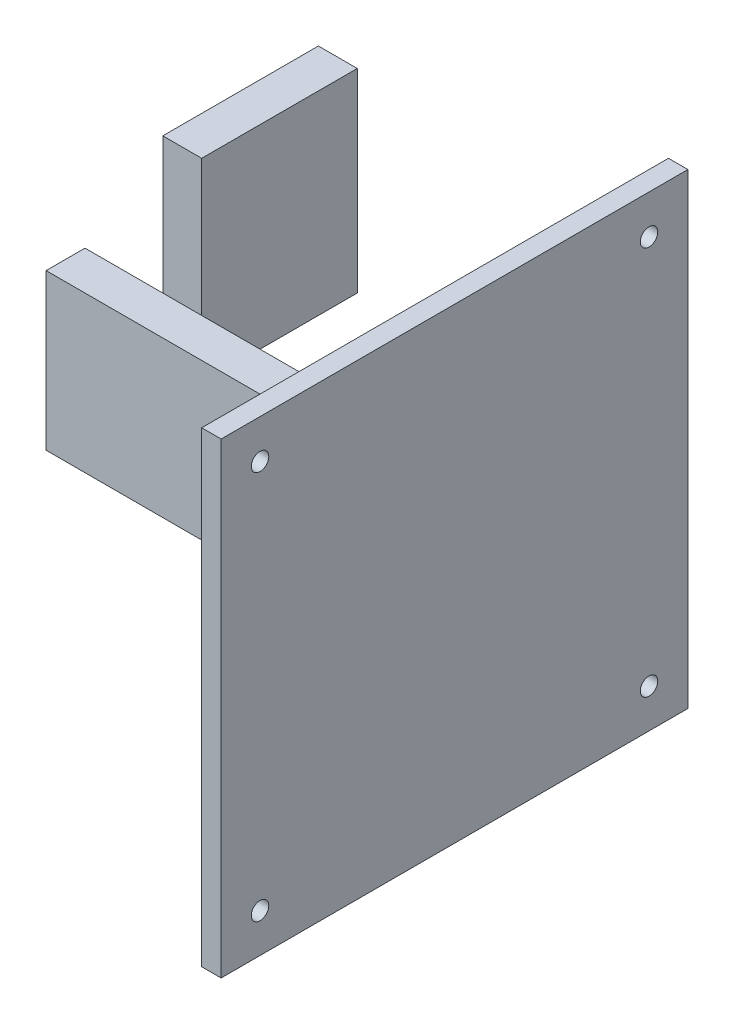
SolidWorks part; units mm, degrees
ref_plane "前视基准面" through (0, 0, 0) normal (0, 0, 1) x (1, 0, 0)
ref_plane "上视基准面" through (0, 0, 0) normal (0, 1, 0) x (1, 0, 0)
ref_plane "右视基准面" through (0, 0, 0) normal (1, 0, 0) x (0, 0, -1)
other "Configuration Table"
sketch "Sketch1" plane through (0, 0, 0) normal (1, 0, 0) x (0, 0, -1)
  line L1 (-20, -25) -> (20, -25)
  line L2 (-20, -25) -> (-20, 25)
  line L3 (-20, 25) -> (20, 25)
  line L4 (20, -25) -> (20, 25)
  line L5 (-20, -25) -> (20, 25) construction
  line L6 (-20, 25) -> (20, -25) construction
  point P0 (0, 0)
extrude "Boss-Extrude1" add sketch "Sketch1" along normal blind 10
ref_plane "Plane1" through (0, 0, 50) normal (0, 0, 1) x (1, 0, 0)
sketch "Sketch2" plane through (0, 0, 50) normal (0, 0, 1) x (1, 0, 0)
  line L1 (10, -20) -> (110, -20)
  line L2 (10, -20) -> (10, 20)
  line L3 (10, 20) -> (110, 20)
  line L4 (110, -20) -> (110, 20)
  line L5 (10, -20) -> (110, 20) construction
  line L6 (10, 20) -> (110, -20) construction
  point P0 (60, 0)
extrude "Boss-Extrude2" add sketch "Sketch2" along normal blind 10
ref_plane "Plane2" through (110, 0, 0) normal (1, 0, 0) x (0, 0, -1)
sketch "Sketch3" plane through (110, 0, 0) normal (1, 0, 0) x (0, 0, -1)
  line L1 (-115, -60) -> (5, -60)
  line L2 (-115, -60) -> (-115, 60)
  line L3 (-115, 60) -> (5, 60)
  line L4 (5, -60) -> (5, 60)
  line L5 (-115, -60) -> (5, 60) construction
  line L6 (-115, 60) -> (5, -60) construction
  point P0 (-55, 0)
extrude "Boss-Extrude3" add sketch "Sketch3" against normal blind 5
sketch "Sketch4" plane through (110, 0, 0) normal (1, 0, 0) x (0, 0, -1)
  circle A0 centre (-105, -50) radius 2.25
  circle A1 centre (-105, 50) radius 2.25
  circle A2 centre (-5, -50) radius 2.25
  circle A3 centre (-5, 50) radius 2.25
extrude "Cut-Extrude1" cut sketch "Sketch4" against normal blind 10
ref_plane "bracket_vertical_back_face" through (0, -20, 0) normal (0, 1, 0) x (1, 0, 0)
ref_plane "bracket_screen_mount_face" through (110, 0, 0) normal (1, 0, 0) x (0, 0, -1)
sketch3d "3DSketch1"
  line L0 (5, 0, 0) -> (5, 0, 100) construction
ref_axis "bracket_rotation_axis" through (5, 0, 0) along (0, 0, 1)
sketch3d "3DSketch2"
  line L0 (110, -50, 105) -> (120, -50, 105) construction
ref_axis "vesa_hole_axis_1" through (110, -50, 105) along (1, 0, 0)
sketch3d "3DSketch3"
  line L0 (110, 50, 105) -> (120, 50, 105) construction
ref_axis "vesa_hole_axis_2" through (110, 50, 105) along (1, 0, 0)
sketch3d "3DSketch4"
  line L0 (110, -50, 5) -> (120, -50, 5) construction
ref_axis "vesa_hole_axis_3" through (110, -50, 5) along (1, 0, 0)
sketch3d "3DSketch5"
  line L0 (110, 50, 5) -> (120, 50, 5) construction
ref_axis "vesa_hole_axis_4" through (110, 50, 5) along (1, 0, 0)
